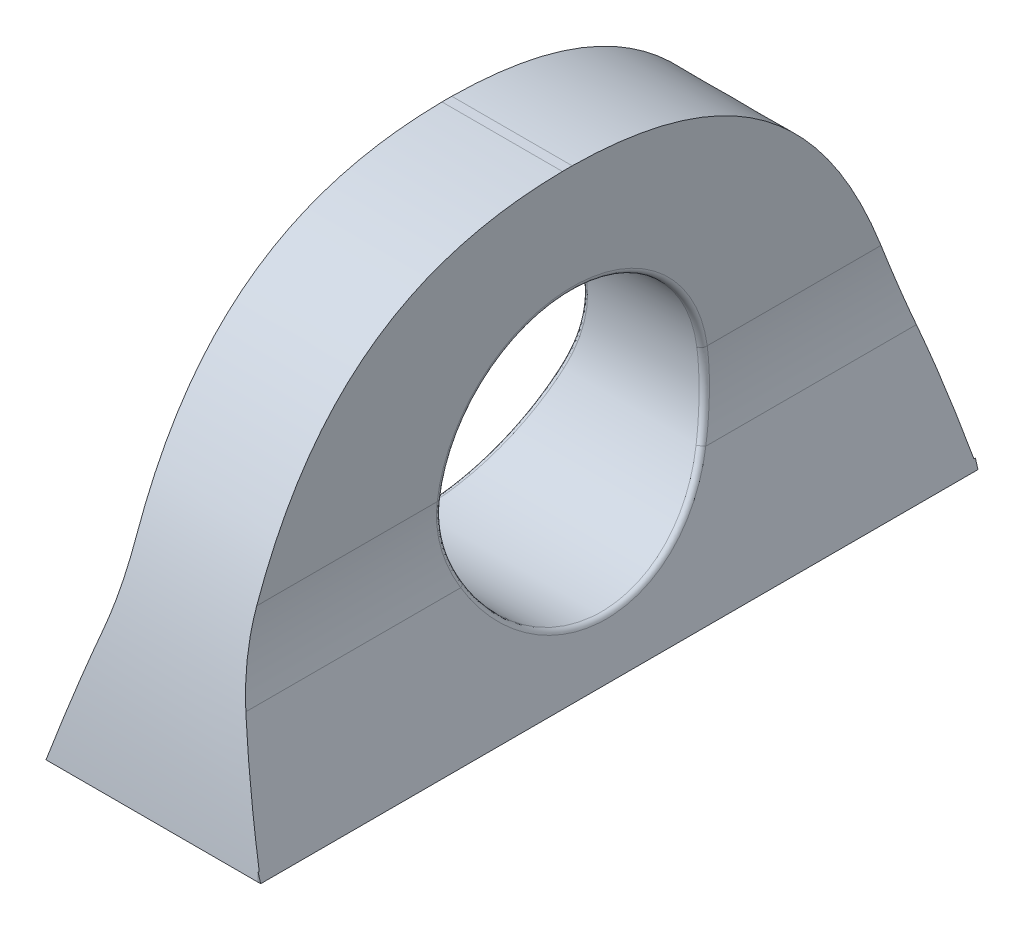
SolidWorks part; units mm, degrees
ref_plane "Front Plane" through (0, 0, 0) normal (0, 0, 1) x (1, 0, 0)
ref_plane "Top Plane" through (0, 0, 0) normal (0, 1, 0) x (1, 0, 0)
ref_plane "Right Plane" through (0, 0, 0) normal (1, 0, 0) x (0, 0, -1)
sketch "Sketch1" plane through (0, 0, 0) normal (0, 0, 1) x (1, 0, 0)
  line L0 (-11.5, 52.9355) -> (11.5, 52.9355)
  line L1 (11.5, 52.9355) -> (11.5, 2.9355)
  line L2 (11.5, 2.9355) -> (20.5, -27.0645)
  line L3 (20.5, -27.0645) -> (-20.5, -27.0645)
  line L5 (-11.5, 2.9355) -> (-20.5, -27.0645)
  line L6 (-11.5, 52.9355) -> (-11.5, 2.9355)
  point P0 (0, 0)
  dimension "D1" = 41
  dimension "D2" = 23
  dimension "D3" = 80
  dimension "D4" = 50
  dimension "D5" = 50
  dimension "D6" = 20.5
  dimension "D7" = 11.5
extrude "Boss-Extrude1" add sketch "Sketch1" against normal blind 137
ref_plane "Plane1" through (20, 0, 0) normal (1, 0, 0) x (0, 0, -1)
sketch "Sketch2" plane through (20, 0, 0) normal (1, 0, 0) x (0, 0, -1)
  line L0 (0, -27.0645) -> (137, -27.0645)
  line L1 (137, 52.9355) -> (0, 52.9355) construction
  circle A0 centre (68.5, 6.9355) radius 25
  spline S0 degree 3 poles (137, -27.0645) (129.4013, 18.6861) (111.2639, 53.048) (22.5359, 53.4192) (5.7329, 17.6855) (0, -27.0645) knots 0 0 0 0 0.436298 0.536298 1 1 1 1
  dimension "D1" = 50
  dimension "D2" = 34
  dimension "D3" = 0
extrude "Cut-Extrude1" cut sketch "Sketch2" against normal blind 100 flip side to cut
fillet "Fillet1" radius 50 4 edges at (11.5, 2.9355, -24.8528) (-11.5, 2.9355, -111.6178) (11.5, 2.9355, -111.6178) (-11.5, 2.9355, -24.8528)
fillet "Fillet2" radius 1 8 edges at (-11.5, 31.9355, -68.5) (11.5, 31.9355, -68.5) (12.1026, 2.5348, -43.8904) (-12.1026, 2.5348, -93.1096) (11.9903, 3.2888, -93.2326) (17.8, -18.0645, -68.5) (-11.9903, 3.2888, -43.7674) (-17.8, -18.0645, -68.5)
